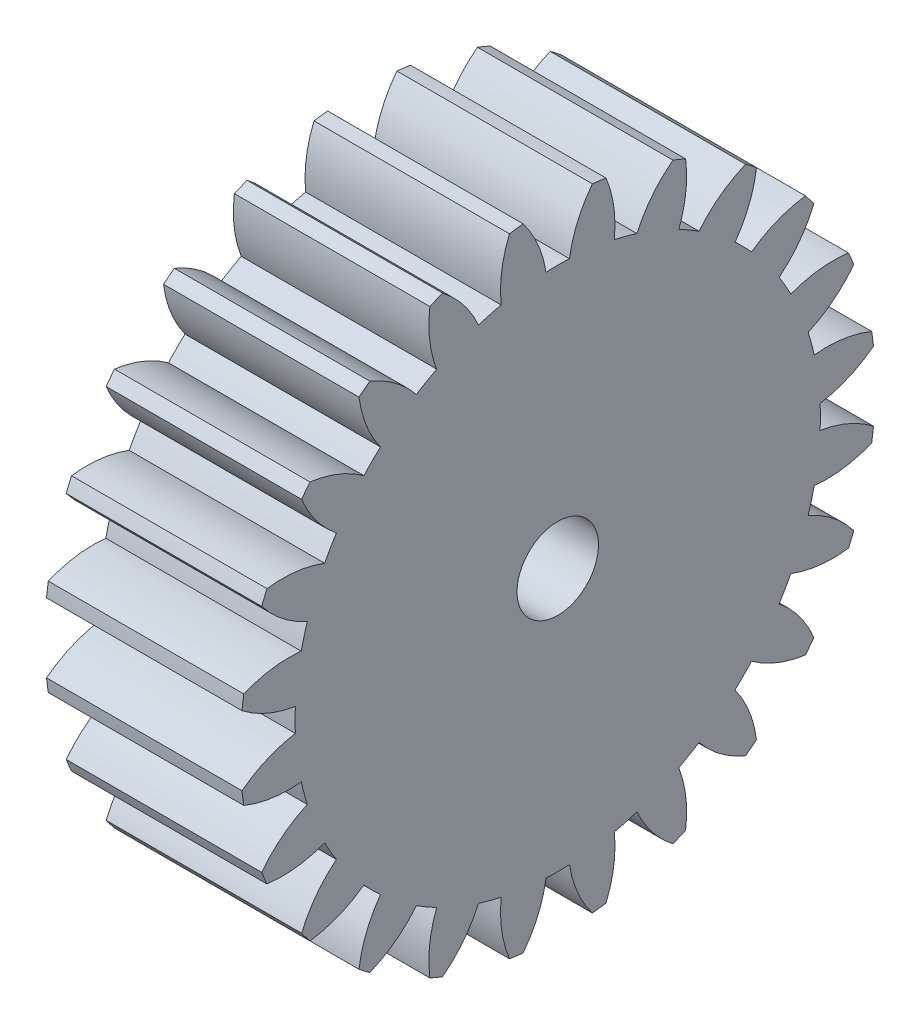
SolidWorks part; units mm, degrees
ref_plane "Plane1" through (0, 0, 0) normal (0, 0, 1) x (1, 0, 0)
ref_plane "Plane2" through (0, 0, 0) normal (0, 1, 0) x (1, 0, 0)
ref_plane "Plane3" through (0, 0, 0) normal (1, 0, 0) x (0, 0, -1)
sketch "HoldingSke" plane through (0, 0, 0) normal (0, 1, 0) x (1, 0, 0)
  line L0 (0, 0) -> (0.609, -0.2712)
  line L1 (-15, 0) -> (100, 0) construction
  line L2 (0, 0) -> (-2.1039, 2.3779)
  line L3 (0, 0) -> (-11.863, 4.5341)
  line L4 (0, 0) -> (7.8894, 3.5126)
  line L5 (0, 0) -> (-46.8476, -17.4728)
  line L6 (0, 0) -> (-9.9476, -6.7116)
  line L7 (-2.1039, 2.3779) -> (8.6586, 51.2059)
  line L8 (-76.2, 54.61) -> (-75.3, 54.61)
  line L9 (-71.009, 38.7566) -> (-53.1078, 45.2721)
  line L10 (-76.2, 71.12) -> (104.1128, 71.12)
  line L11 (0, 0) -> (-12, 0)
  line L12 (-76.2, 101.6) -> (-76.147, 101.6)
  line L13 (24.9733, 27.94) -> (52.9518, 28.4284)
  line L14 (24.9733, 27.94) -> (24.9743, 27.94)
  line L15 (24.9733, 27.94) -> (100.4006, 29.5858)
  line L16 (-63.627, -1.5) -> (-12.827, -1.5)
  circle A0 centre (0, 0) radius 2.5
  circle A1 centre (0, 0) radius 16.124
  circle A2 centre (0, 0) radius 37.5
  circle A3 centre (0, 0) radius 2.5
  dimension "Num_teeth" = 24
  dimension "Pitch_radius" = 180.3128
  dimension "Width" = 12
  dimension "Thickness" = 12
sketch "BasProSke" plane through (0, 0, 0) normal (0, 1, 0) x (1, 0, 0)
  line L0 (-10, 0) -> (60, 0) construction
  line L1 (0, 0) -> (0, 19.5)
  line L2 (0, 0) -> (12, 0)
  line L3 (12, 0) -> (12, 19.5)
  line L4 (12, 19.5) -> (0, 19.5)
  dimension "Thickness" = 12
  dimension "Diameter" = 39
revolve "Base-Revolve" add sketch "BasProSke" angle 360 about L0
sketch "TooCutSke" plane through (0, 0, 0) normal (1, 0, 0) x (0, 0, -1)
  line L1 (0, 0) -> (0, 107) construction
  line L2 (0, 0) -> (-1.27, 17.9551) construction
  line L3 (0, 0) -> (-4.6904, 35.6272) construction
  line L4 (-1.27, 17.9551) -> (-2.3452, 17.8136) construction
  arc A0 (0.719, 16.108) -> (-0.719, 16.108) centre (0, 0) ccw
  arc A1 (2.1447, 19.4073) -> (-2.1447, 19.4073) centre (0, 0) ccw
  circle A2 centre (0, 0) radius 18 construction
  circle A3 centre (0, 0) radius 16.9145 construction
  arc A4 (-0.719, 16.108) -> (-2.1447, 19.4073) centre (-7.832, 14.992) ccw
  arc A5 (2.1447, 19.4073) -> (0.719, 16.108) centre (7.832, 14.992) ccw
extrude "ToothCut" cut sketch "TooCutSke" along normal through all
fillet "Breaks" [suppressed] radius 0.03 tangent propagation no
fillet "RootFillets" [suppressed] radius 0.376
pattern_circular "TeethCuts" count 24 every 15 about axis through (-10, 0, 0) along (1, 0, 0) of "ToothCut", "RootFillets", "Breaks"
sketch "HubNeaOneSke" plane through (0, 0, 0) normal (-1, 0, 0) x (0, 0, 1)
  circle A0 centre (0, 0) radius 16.124
  dimension "Diameter" = 32.248
extrude "HubNearOne" [suppressed] add sketch "HubNeaOneSke" along normal blind 38.0001
sketch "HubNeaBotSke" plane through (0, 0, 0) normal (-1, 0, 0) x (0, 0, 1)
  circle A0 centre (0, 0) radius 16.124
  dimension "Diameter" = 32.248
extrude "HubNearBoth" [suppressed] add sketch "HubNeaBotSke" along normal blind 19
ref_plane "FarPln" through (12, 0, 0) normal (1, 0, 0) x (0, 0, -1)
sketch "HubFarSke" plane through (12, 0, 0) normal (1, 0, 0) x (0, 0, -1)
  circle A0 centre (0, 0) radius 16.124
  dimension "Diameter" = 32.248
extrude "HubFar" [suppressed] add sketch "HubFarSke" along normal blind 19
sketch "BorSke" plane through (0, 0, 0) normal (1, 0, 0) x (0, 0, -1)
  circle A0 centre (0, 0) radius 2.5
  dimension "Diameter" = 5
extrude "Bore" cut sketch "BorSke" along normal mid plane 100.0001
sketch "KeySke" plane through (0, 0, 0) normal (1, 0, 0) x (0, 0, -1)
  line L0 (-1, 0) -> (-1, 3.4)
  line L1 (-1, 3.4) -> (1, 3.4)
  line L2 (1, 3.4) -> (1, 0)
  line L3 (0, 0) -> (0, 34) construction
  line L4 (-1, 0) -> (1, 0)
  dimension "Width" = 2
extrude "Keyway" [suppressed] cut sketch "KeySke" along normal mid plane 100.0001
pattern_circular "Keyway2" [suppressed] count 2 every 90 about axis through (-10, 0, 0) along (1, 0, 0) reverse direction yes
sketch "Sketch1" plane through (0, 0, 0) normal (-1, 0, 0) x (0, 0, 1)
  line L0 (-2, 1.5) -> (2, 1.5)
  circle A0 centre (0, 0) radius 2.5
  dimension "D1" = 5
  dimension "D2" = 1.5
extrude "Boss-Extrude1" add sketch "Sketch1" against normal blind 10 contours L0 A0 region at (0, 1.9078, 0)
equation "' \"Module@HoldingSke\" = 6.35"
equation "' \"Num_teeth@HoldingSke\" = 12"
equation "' \"Ap@HoldingSke\" =  20"
equation "' \"Ap@HoldingSke\" = 20"
equation "' \"Width@HoldingSke\" = 0.5 * 25.4"
equation "' \"Hub_dia@HoldingSke\"= 1 * 25.4"
equation "' \"Hub_dia@HoldingSke\" = 1 * 25.4"
equation "' \"Overall_len@HoldingSke\" = 1.0 * 25.4"
equation "' \"Bore@HoldingSke\" = 0.75 * 25.4"
equation "' \"T_dim@HoldingSke\" = 0.1 * 25.4"
equation "' \"Width@KeySke\" = 0.25 * 25.4"
equation "' \"Show_teeth@HoldingSke\" = 13"
equation "' \"Backlash@HoldingSke\" = 0.009 * 25.4"
equation "' \"Addendum_fac@HoldingSke\" = 1.0"
equation "' \"Dedendum_fac@HoldingSke\" = 1.25"
equation "' \"Dedendum_add@HoldingSke\" = 0.00005 * 25.4"
equation "' \"Clearance_fac@HoldingSke\" = 0.25"
equation "\"Pitch@HoldingSke\" = 1 / \"Module@HoldingSke\""
equation "\"Overcut_dia@TooCutSke\" = (\"Num_teeth@HoldingSke\" + 2 * \"Addendum_fac@HoldingSke\") / \"Pitch@HoldingSke\" + 0.002 * 25.4"
equation "\"Pitch_dia@TooCutSke\" = \"Num_teeth@HoldingSke\" / \"Pitch@HoldingSke\""
equation "\"Base_dia@TooCutSke\" = \"Num_teeth@HoldingSke\" / \"Pitch@HoldingSke\" * cos((\"Ap@HoldingSke\"  * 3.14159265 / 180))"
equation "\"Root_dia@TooCutSke\" = (\"Num_teeth@HoldingSke\" + 2) / \"Pitch@HoldingSke\" - 2 * (\"Addendum_fac@HoldingSke\" + \"Dedendum_fac@HoldingSke\") / \"Pitch@HoldingSke\" - \"Dedendum_add@HoldingSke\" * 2"
equation "\"Half_ang@TooCutSke\" = 180 / \"Num_teeth@HoldingSke\""
equation "\"Half_CT@TooCutSke\" = \"Num_teeth@HoldingSke\" / \"Pitch@HoldingSke\" * sin((3.14159265 / 2 / \"Num_teeth@HoldingSke\")) / 2 - 7 * \"Backlash@HoldingSke\" / 4"
equation "\"Flank_rad@TooCutSke\" = \"Num_teeth@HoldingSke\" / \"Pitch@HoldingSke\" / 5"
equation "\"Radius@RootFillets\" = \"Clearance_fac@HoldingSke\" / \"Pitch@HoldingSke\" + \"Dedendum_add@HoldingSke\""
equation "\"Break_rad@Breaks\" = 0.02 / \"Pitch@HoldingSke\""
equation "\"Thickness@HoldingSke\" = \"Width@HoldingSke\""
equation "\"OAL@HoldingSke\" = \"Thickness@HoldingSke\""
equation "\"MHD@HoldingSke\" = (\"Num_teeth@HoldingSke\" + 2) / \"Pitch@HoldingSke\" - 2 * (\"Addendum_fac@HoldingSke\" + \"Dedendum_fac@HoldingSke\")  / \"Pitch@HoldingSke\" - \"Dedendum_add@HoldingSke\" * 2"
equation "\"MBD@HoldingSke\" = (\"Num_teeth@HoldingSke\" + 2) / \"Pitch@HoldingSke\" - 2 * (\"Addendum_fac@HoldingSke\" + \"Dedendum_fac@HoldingSke\")  / \"Pitch@HoldingSke\" - \"Dedendum_add@HoldingSke\" * 2 - 0.002 * 25.4"
equation "\"MHD@HoldingSke\" = ((sgn( \"MHD@HoldingSke\" - \"Hub_dia@HoldingSke\" )-1)*( \"MHD@HoldingSke\" - \"Hub_dia@HoldingSke\" ))/-2+ \"Hub_dia@HoldingSke\""
equation "\"MBD@HoldingSke\" = ((sgn( \"MBD@HoldingSke\" - \"Bore@HoldingSke\" )-1)*( \"MBD@HoldingSke\" - \"Bore@HoldingSke\" ))/-2+ \"Bore@HoldingSke\""
equation "\"OAL@HoldingSke\" = ((sgn( \"OAL@HoldingSke\" - \"Overall_len@HoldingSke\" )+1)*( \"OAL@HoldingSke\" - \"Overall_len@HoldingSke\" ))/2 + \"Overall_len@HoldingSke\" + 0.000002 * 25.4"
equation "\"Num_teeth@TeethCuts\" = int( \"Show_teeth@HoldingSke\" ) + 1"
equation "\"Num_teeth@TeethCuts\" = ((sgn( \"Num_teeth@TeethCuts\" - \"Num_teeth@HoldingSke\" )-1)*( \"Num_teeth@TeethCuts\" - \"Num_teeth@HoldingSke\" ))/-2+ \"Num_teeth@HoldingSke\""
equation "\"Num_teeth@TeethCuts\" = ((sgn( \"Num_teeth@TeethCuts\" - 2.0)+1)*( \"Num_teeth@TeethCuts\" - 2.0))/2 +2.0"
equation "\"Angle@TeethCuts\" = 360.0 / \"Num_teeth@HoldingSke\""
equation "\"Diameter@BasProSke\" = (\"Num_teeth@HoldingSke\" + 2 * \"Addendum_fac@HoldingSke\") / \"Pitch@HoldingSke\""
equation "\"Thickness@BasProSke\"  = \"Thickness@HoldingSke\""
equation "' \"Fillet_rad@BasProSke\" =  \"Thickness@HoldingSke\" * 0.05"
equation "' \"Fillet_rad@BasProSke\" = \"Thickness@HoldingSke\" * 0.05"
equation "\"MHD@HoldingSke\" = ((sgn( \"MHD@HoldingSke\" - \"Root_dia@TooCutSke\" )-1)*( \"MHD@HoldingSke\" - \"Root_dia@TooCutSke\" ))/-2+ \"Root_dia@TooCutSke\""
equation "\"Diameter@HubNeaOneSke\" = \"MHD@HoldingSke\""
equation "\"Length@HubNearOne\" = \"OAL@HoldingSke\" - \"Thickness@BasProSke\""
equation "\"Diameter@HubNeaBotSke\" = \"MHD@HoldingSke\""
equation "\"Length@HubNearBoth\" = ( \"OAL@HoldingSke\" - \"Thickness@BasProSke\" ) / 2.0"
equation "\"Thickness@FarPln\" = \"Thickness@BasProSke\""
equation "\"Diameter@HubFarSke\" = \"MHD@HoldingSke\""
equation "\"Length@HubFar\" = ( \"OAL@HoldingSke\" - \"Thickness@BasProSke\" ) / 2.0"
equation "\"Diameter@BorSke\" = \"MBD@HoldingSke\""
equation "\"D1@Bore\" = \"OAL@HoldingSke\" * 2.0"
equation "\"D1@Keyway\" = \"OAL@HoldingSke\" * 2.0"
equation "\"Offset@KeySke\" = \"T_dim@HoldingSke\" + \"MBD@HoldingSke\" / 2.0"
